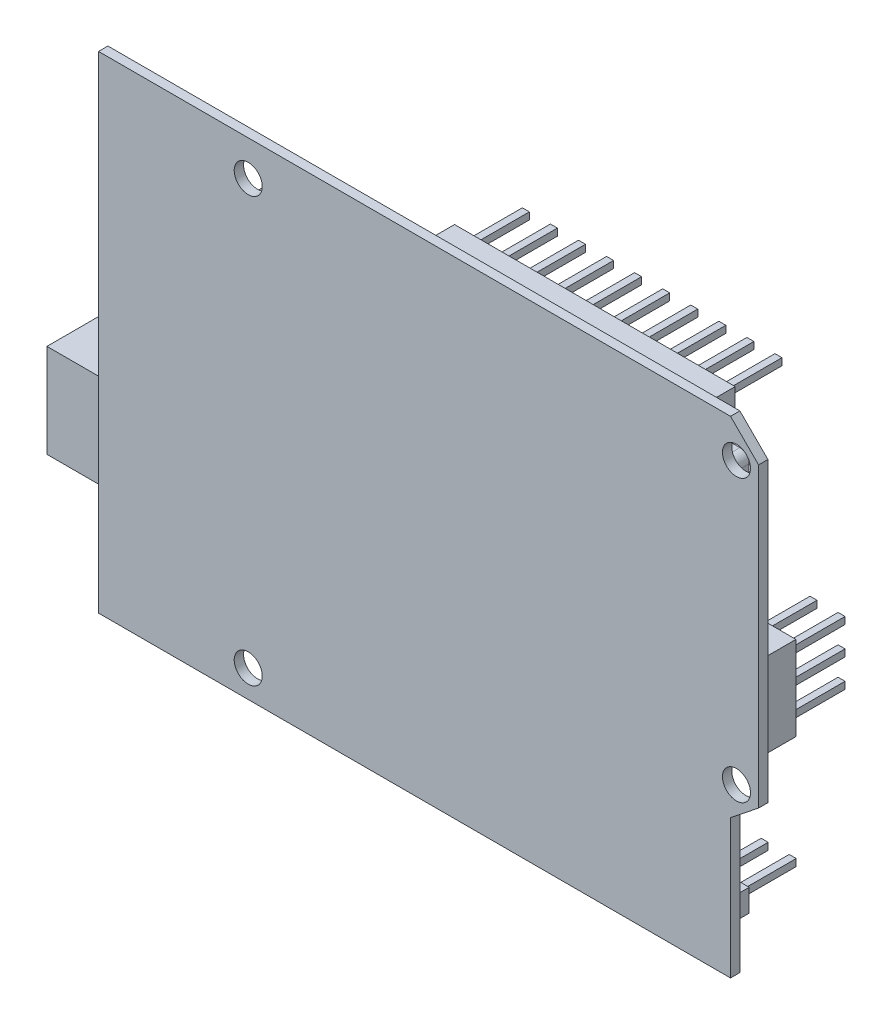
SolidWorks part; units mm, degrees
ref_plane "Front Plane" through (0, 0, 0) normal (0, 0, 1) x (1, 0, 0)
ref_plane "Top Plane" through (0, 0, 0) normal (0, 1, 0) x (1, 0, 0)
ref_plane "Right Plane" through (0, 0, 0) normal (1, 0, 0) x (0, 0, -1)
sketch "Sketch1" plane through (0, 0, 0) normal (0, 0, 1) x (1, 0, 0)
  line L0 (22.754, 124.2709) -> (19.754, 127.2709)
  line L1 (19.754, 75.2709) -> (-47.7999, 75.2709)
  line L2 (22.754, 92.5002) -> (22.754, 124.2709)
  line L3 (19.754, 127.2709) -> (-47.7999, 127.2709)
  line L4 (-47.7999, 75.2709) -> (-47.7999, 127.2709)
  line L5 (22.754, 92.5002) -> (19.754, 90.1139)
  line L6 (19.754, 90.1139) -> (19.754, 75.2709)
  dimension "D1" = 135
  dimension "D2" = 3
  dimension "D3" = 3
extrude "Boss-Extrude1" add sketch "Sketch1" against normal blind 1
sketch "Sketch2" plane through (0, 0, -1) normal (0, 0, -1) x (-1, 0, 0)
  line L1 (38.3165, 86.2081) -> (54.3165, 86.2081)
  line L2 (38.3165, 86.2081) -> (38.3165, 96.2081)
  line L3 (38.3165, 96.2081) -> (54.3165, 96.2081)
  line L4 (54.3165, 86.2081) -> (54.3165, 96.2081)
  dimension "D1" = 16
  dimension "D2" = 10
extrude "Boss-Extrude2" add sketch "Sketch2" along normal blind 10
sketch "Sketch3" plane through (-54.3165, 0, 0) normal (-1, 0, 0) x (0, 0, 1)
  line L1 (-8.51, 88.5529) -> (-3.6209, 88.5529)
  line L2 (-8.51, 88.5529) -> (-8.51, 93.9309)
  line L3 (-8.51, 93.9309) -> (-3.6209, 93.9309)
  line L4 (-3.6209, 88.5529) -> (-3.6209, 93.9309)
extrude "Cut-Extrude1" cut sketch "Sketch3" against normal blind 10
sketch "Sketch4" plane through (0, 0, -1) normal (0, 0, -1) x (-1, 0, 0)
  line L0 (47.7999, 75.2709) -> (-19.754, 75.2709) construction
  line L1 (-16.754, 77.2709) -> (28.246, 77.2709)
  line L2 (-16.754, 77.2709) -> (-16.754, 79.6709)
  line L3 (-16.754, 79.6709) -> (28.246, 79.6709)
  line L4 (28.246, 77.2709) -> (28.246, 79.6709)
  line L5 (-15.254, 125.2709) -> (14.746, 125.2709)
  line L6 (-15.254, 125.2709) -> (-15.254, 122.8709)
  line L7 (-15.254, 122.8709) -> (14.746, 122.8709)
  line L8 (14.746, 125.2709) -> (14.746, 122.8709)
  line L9 (-19.754, 127.2709) -> (47.7999, 127.2709) construction
  line L10 (-22.754, 92.5002) -> (-22.754, 124.2709) construction
  line L11 (-19.754, 75.2709) -> (-19.754, 90.1139) construction
  dimension "D1" = 2.4
  dimension "D2" = 2.4
  dimension "D3" = 2
  dimension "D4" = 2
  dimension "D5" = 7.5
  dimension "D6" = 3
  dimension "D7" = 45
  dimension "D8" = 30
extrude "Boss-Extrude3" add sketch "Sketch4" along normal blind 4
sketch "Sketch5" plane through (0, 0, -1) normal (0, 0, -1) x (-1, 0, 0)
  line L0 (-15.254, 122.8709) -> (14.746, 122.8709) construction
  line L1 (-13.754, 118.3709) -> (21.246, 118.3709)
  line L2 (-13.754, 118.3709) -> (-13.754, 108.3709)
  line L3 (-13.754, 108.3709) -> (21.246, 108.3709)
  line L4 (21.246, 118.3709) -> (21.246, 108.3709)
  line L5 (-22.754, 92.5002) -> (-22.754, 124.2709) construction
  dimension "D1" = 10
  dimension "D2" = 35
  dimension "D3" = 4.5
  dimension "D4" = 9
extrude "Boss-Extrude4" add sketch "Sketch5" along normal blind 7
sketch "Sketch6" plane through (0, 0, -8) normal (0, 0, -1) x (-1, 0, 0)
  line L0 (21.246, 108.3709) -> (21.246, 118.3709) construction
  line L1 (-13.754, 118.3709) -> (21.246, 118.3709)
  line L2 (-13.754, 118.3709) -> (-13.754, 116.8709)
  line L3 (-13.754, 116.8709) -> (21.246, 116.8709)
  line L4 (21.246, 118.3709) -> (21.246, 116.8709)
  line L6 (-13.754, 108.3709) -> (21.246, 108.3709)
  line L7 (-13.754, 108.3709) -> (-13.754, 109.8709)
  line L8 (-13.754, 109.8709) -> (21.246, 109.8709)
  line L9 (21.246, 108.3709) -> (21.246, 109.8709)
  dimension "D1" = 1.5
  dimension "D2" = 1.5
extrude "Cut-Extrude2" cut sketch "Sketch6" against normal blind 4
fillet "Fillet1" radius 1 4 edges at (-21.246, 116.8709, -6) (-21.246, 109.8709, -6) (13.754, 116.8709, -6) (13.754, 109.8709, -6)
sketch "Sketch7" plane through (0, 0, -1) normal (0, 0, -1) x (-1, 0, 0)
  line L0 (47.7999, 127.2709) -> (47.7999, 96.2081) construction
  line L1 (47.7999, 86.2081) -> (47.7999, 75.2709) construction
  circle A0 centre (-20.3905, 123.5068) radius 1.5
  circle A1 centre (-20.3905, 93.4803) radius 1.5
  circle A2 centre (31.7999, 123.5068) radius 1.5
  circle A3 centre (31.7999, 78.1921) radius 1.5
  dimension "D1" = 3
  dimension "D2" = 3
  dimension "D3" = 16
  dimension "D4" = 16
  dimension "D5" = 3
  dimension "D6" = 3
extrude "Cut-Extrude3" cut sketch "Sketch7" against normal blind 4
sketch "Sketch8" plane through (0, 0, -5) normal (0, 0, -1) x (-1, 0, 0)
  line L0 (-15.254, 124.0709) -> (14.746, 124.0709) construction
  line L1 (-14.254, 124.4459) -> (-13.504, 124.4459)
  line L2 (-14.254, 124.4459) -> (-14.254, 123.6959)
  line L3 (-14.254, 123.6959) -> (-13.504, 123.6959)
  line L4 (-13.504, 124.4459) -> (-13.504, 123.6959)
  line L5 (-15.254, 125.2709) -> (-15.254, 122.8709) construction
  line L6 (14.746, 122.8709) -> (14.746, 125.2709) construction
  dimension "D1" = 0.75
  dimension "D2" = 0.75
  dimension "D3" = 0.375
  dimension "D4" = 1
extrude "Boss-Extrude5" add sketch "Sketch8" along normal blind 6
pattern_linear "LPattern1" count 10 spacing 3 along (-1, 0, 0) of "Boss-Extrude5"
sketch "Sketch9" plane through (0, 0, -5) normal (0, 0, -1) x (-1, 0, 0)
  line L0 (-16.754, 78.4709) -> (28.246, 78.4709) construction
  line L1 (-16.754, 79.6709) -> (-16.754, 77.2709) construction
  line L2 (28.246, 77.2709) -> (28.246, 79.6709) construction
  line L4 (-15.7778, 78.8459) -> (-15.0278, 78.8459)
  line L5 (-15.7778, 78.8459) -> (-15.7778, 78.0959)
  line L6 (-15.7778, 78.0959) -> (-15.0278, 78.0959)
  line L7 (-15.0278, 78.8459) -> (-15.0278, 78.0959)
  dimension "D1" = 0.75
  dimension "D2" = 0.75
  dimension "D3" = 0.375
extrude "Boss-Extrude6" add sketch "Sketch9" along normal blind 6
pattern_linear "LPattern2" count 15 spacing 3 along (-1, 0, 0) of "Boss-Extrude6"
sketch "Sketch10" plane through (0, 0, -1) normal (0, 0, -1) x (-1, 0, 0)
  circle A0 centre (26.5467, 118.215) radius 2.5
  circle A1 centre (31.9407, 118.215) radius 2.5
  dimension "D1" = 5
  dimension "D2" = 5
extrude "Boss-Extrude7" add sketch "Sketch10" along normal blind 6
sketch "Sketch11" plane through (0, 0, -1) normal (0, 0, -1) x (-1, 0, 0)
  line L1 (-21.7492, 96.1139) -> (-16.9492, 96.1139)
  line L2 (-21.7492, 96.1139) -> (-21.7492, 105.1139)
  line L3 (-21.7492, 105.1139) -> (-16.9492, 105.1139)
  line L4 (-16.9492, 96.1139) -> (-16.9492, 105.1139)
  dimension "D1" = 4.8
  dimension "D2" = 9
  dimension "D3" = 6
extrude "Boss-Extrude8" add sketch "Sketch11" along normal up to surface (4 mm away) up to face at (0.254, 124.0709, -5)
sketch "Sketch12" plane through (0, 0, -5) normal (0, 0, -1) x (-1, 0, 0)
  line L0 (-21.7492, 96.1139) -> (-16.9492, 96.1139) construction
  line L1 (-20.9992, 97.8639) -> (-20.2492, 97.8639)
  line L2 (-20.9992, 97.8639) -> (-20.9992, 97.1139)
  line L3 (-20.9992, 97.1139) -> (-20.2492, 97.1139)
  line L4 (-20.2492, 97.8639) -> (-20.2492, 97.1139)
  line L5 (-21.7492, 105.1139) -> (-21.7492, 96.1139) construction
  dimension "D1" = 0.75
  dimension "D2" = 0.75
  dimension "D3" = 1
  dimension "D4" = 0.75
extrude "Boss-Extrude9" add sketch "Sketch12" along normal blind 6
pattern_linear "LPattern3" count 3 spacing 3 along (0, 1, 0) count 2 spacing 3 along (-1, 0, 0) of "Boss-Extrude9"
sketch "Sketch13" plane through (0, 0, -1) normal (0, 0, -1) x (-1, 0, 0)
  line L1 (16.3872, 103.9285) -> (30.5081, 103.9285)
  line L2 (16.3872, 103.9285) -> (16.3872, 99.5659)
  line L3 (16.3872, 99.5659) -> (30.5081, 99.5659)
  line L4 (30.5081, 103.9285) -> (30.5081, 99.5659)
extrude "Boss-Extrude10" add sketch "Sketch13" along normal blind 4
fillet "Fillet2" radius 1 4 edges at (-30.5081, 103.9285, -3) (-30.5081, 99.5659, -3) (-16.3872, 103.9285, -3) (-16.3872, 99.5659, -3)
